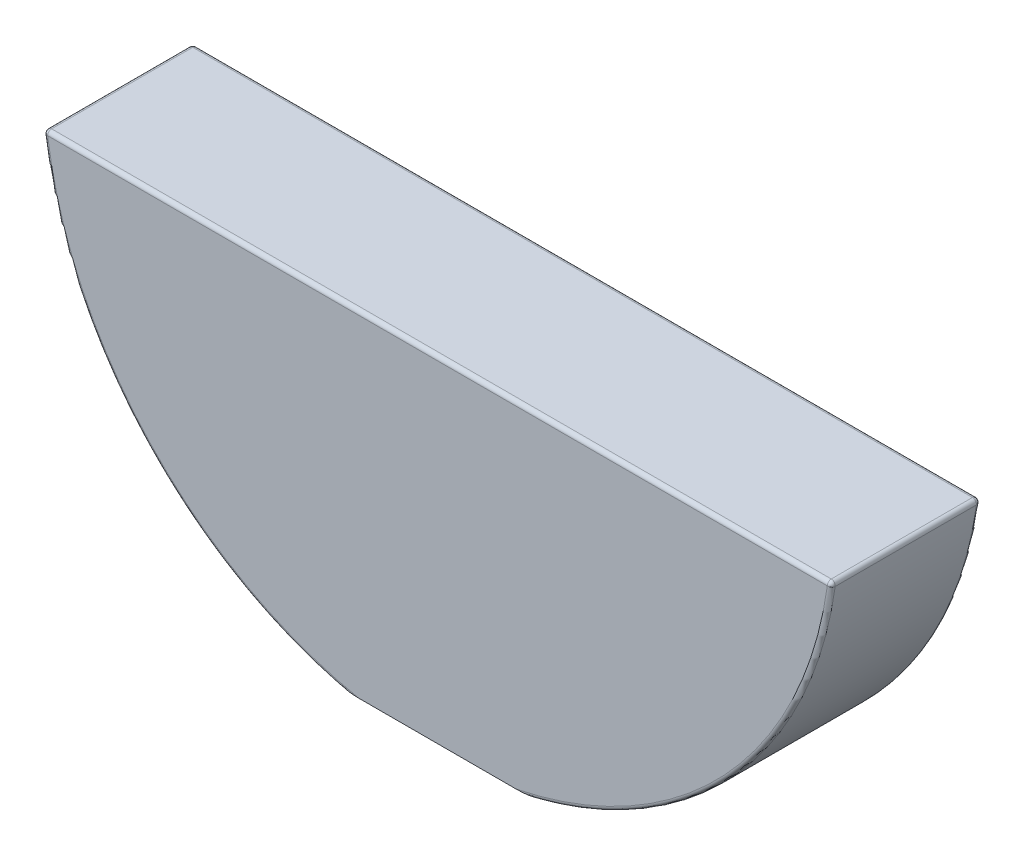
SolidWorks part; units mm, degrees
material "A-1"
ref_plane "Front Plane" through (0, 0, 0) normal (0, 0, 1) x (1, 0, 0)
ref_plane "Top Plane" through (0, 0, 0) normal (0, 1, 0) x (1, 0, 0)
ref_plane "Right Plane" through (0, 0, 0) normal (1, 0, 0) x (0, 0, -1)
sketch "Sketch1" plane through (0, 0, 0) normal (0, 0, 1) x (1, 0, 0)
  line L0 (-73.722, 0) -> (74.6512, 0) construction
  line L1 (-12.5988, -1.6002) -> (12.5988, -1.6002)
  arc A0 (-12.5988, -1.6002) -> (12.5988, -1.6002) centre (0, 0) ccw
  dimension "Breadth" = 25.4
  dimension "Excursion" = 1.6002
extrude "Extrude1" add sketch "Sketch1" along normal blind 4.7625
fillet "Fillet3" radius 0.127 6 edges at (12.5988, -1.6002, 2.3813) (-12.5988, -1.6002, 2.3813) (0, -1.6002, 4.7625) (0, -12.7, 4.7625) (0, -1.6002, 0) (0, -12.7, 0)
sketch "Sketch3" plane through (0, 0, 0) normal (0, 0, 1) x (1, 0, 0)
  line L0 (-50.8, -12.319) -> (50.8, -12.319)
  line L2 (-12.4538, -1.6002) -> (12.4538, -1.6002) construction
  dimension "D1" = 50.8
  dimension "D2" = 101.6
  dimension "High" = 10.7188
extrude "Cut-Extrude2" cut sketch "Sketch3" along normal through all and the other way through all flip side to cut
sketch "Sketch2" plane through (0, 0, 0) normal (0, 0, 1) x (1, 0, 0)
  line L0 (-2.54, 0) -> (-2.54, -50.8)
  line L1 (0, 0) -> (0, -50.8) construction
  dimension "D1" = 50.8
  dimension "Length" = 5.08
extrude "Cut-Extrude1" [suppressed] cut sketch "Sketch2" against normal through all and the other way through all flip side to cut
mirror "Mirror1" [suppressed] about plane through (0, 0, 0) normal (1, 0, 0)
equation "\"Radius@Fillet3\" = \"Width@Extrude1\"*2/75"
